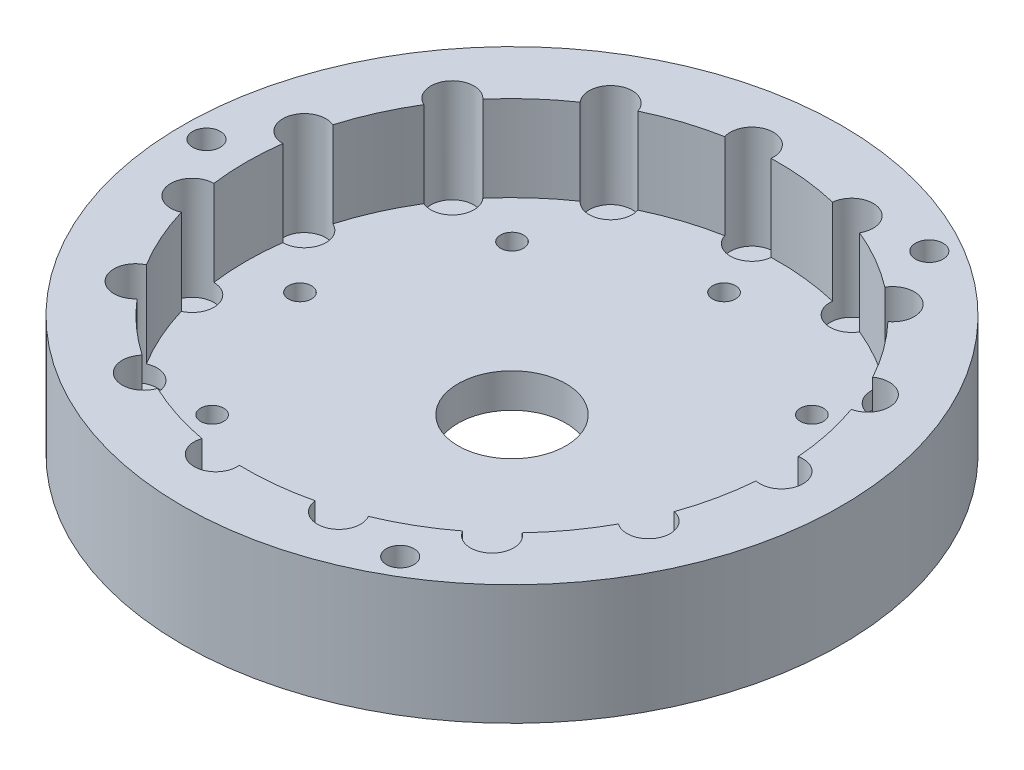
SolidWorks part; units mm, degrees
ref_plane "Front Plane" through (0, 0, 0) normal (0, 0, 1) x (1, 0, 0)
ref_plane "Top Plane" through (0, 0, 0) normal (0, 1, 0) x (1, 0, 0)
ref_plane "Right Plane" through (0, 0, 0) normal (1, 0, 0) x (0, 0, -1)
sketch "Sketch1" plane through (0, 0, 0) normal (0, 1, 0) x (1, 0, 0)
  line L0 (0, 0) -> (-42.5, 0) construction
  circle A0 centre (0, 0) radius 7.5
  circle A1 centre (0, 0) radius 45.85
  circle A2 centre (0, 0) radius 37.5 construction
  circle A3 centre (37.5, 0) radius 3
  circle A4 centre (34.258, 15.2526) radius 3
  circle A5 centre (25.0924, 27.8679) radius 3
  circle A6 centre (11.5881, 35.6646) radius 3
  circle A7 centre (-3.9198, 37.2946) radius 3
  circle A8 centre (-18.75, 32.476) radius 3
  circle A9 centre (-30.3381, 22.0419) radius 3
  circle A10 centre (-36.6805, 7.7967) radius 3
  circle A11 centre (-36.6805, -7.7967) radius 3
  circle A12 centre (-30.3381, -22.0419) radius 3
  circle A13 centre (-18.75, -32.476) radius 3
  circle A14 centre (-3.9198, -37.2946) radius 3
  circle A15 centre (11.5881, -35.6646) radius 3
  circle A16 centre (25.0924, -27.8679) radius 3
  circle A17 centre (34.258, -15.2526) radius 3
  circle A19 centre (0, 0) radius 29.5 construction
  circle A20 centre (29.5, 0) radius 1.607
  circle A21 centre (20.8597, -20.8597) radius 1.607
  circle A22 centre (0, -29.5) radius 1.607
  circle A23 centre (-20.8597, -20.8597) radius 1.607
  circle A24 centre (-29.5, 0) radius 1.607
  circle A25 centre (-20.8597, 20.8597) radius 1.607
  circle A26 centre (0, 29.5) radius 1.607
  circle A27 centre (20.8597, 20.8597) radius 1.607
  arc A28 (36.8833, 2.9359) -> (34.8888, 12.3197) centre (0, 0) ccw
  arc A29 (34.8888, -12.3197) -> (36.8833, -2.9359) centre (0, 0) ccw
  arc A30 (26.8616, -25.4451) -> (32.5004, -17.6839) centre (0, 0) ccw
  arc A31 (14.1898, -34.1709) -> (22.4979, -29.3742) centre (0, 0) ccw
  arc A32 (-0.9355, -36.9882) -> (8.6053, -35.9854) centre (0, 0) ccw
  arc A33 (-15.8991, -33.4099) -> (-6.7752, -36.3744) centre (0, 0) ccw
  arc A34 (-28.1135, -24.0547) -> (-20.9843, -30.4739) centre (0, 0) ccw
  arc A35 (-35.4669, -10.5403) -> (-31.5649, -19.3043) centre (0, 0) ccw
  arc A36 (-36.6878, 4.7967) -> (-36.6878, -4.7967) centre (0, 0) ccw
  arc A37 (-31.5649, 19.3043) -> (-35.4669, 10.5403) centre (0, 0) ccw
  arc A38 (-20.9843, 30.4739) -> (-28.1135, 24.0547) centre (0, 0) ccw
  arc A39 (-6.7752, 36.3744) -> (-15.8991, 33.4099) centre (0, 0) ccw
  arc A40 (8.6053, 35.9854) -> (-0.9355, 36.9882) centre (0, 0) ccw
  arc A41 (22.4979, 29.3742) -> (14.1898, 34.1709) centre (0, 0) ccw
  arc A42 (32.5004, 17.6839) -> (26.8616, 25.4451) centre (0, 0) ccw
  circle A43 centre (-42.5, 0) radius 1.5635
  circle A44 centre (21.25, 36.8061) radius 1.5635
  circle A45 centre (21.25, -36.8061) radius 1.5635
  point P38 (0, 0)
  point P57 (0, 0)
  point P87 (0, 0)
  point P92 (0, 0)
  dimension "D2" = 15
  dimension "D3" = 75
  dimension "D4" = 91.7
  dimension "D5" = 6
  dimension "D8" = 3.214
  dimension "D9" = 59
  dimension "D6" = 37
  dimension "D12" = 3.127
  dimension "D11" = 42.5
  dimension "D1" = 15
  dimension "D7" = 8
  dimension "D10" = 15
  dimension "D13" = 3
extrude "Boss-Extrude1" add sketch "Sketch1" against normal blind 4.7625 contours A4 A42 A5 A41 A6 A40 A7 A39 A8 A38 A9 A37 A10 A36 A11 A35 A12 A34 A13 A33 A14 A32 A15 A31 A16 A30 A17 A29 A3 A28 A0 A20 A21 A22 A23 A24 A25 A26 A27 | A3 | A17 | A4 | A5 | A6 | A7 | A8 | A9 | A10 | A11 | A12 | A13 | A14 | A15 | A16 | A1 A42 A4 A28 A3 A29 A17 A30 A16 A31 A15 A32 A14 A33 A13 A34 A12 A35 A11 A36 A10 A37 A9 A38 A8 A39 A7 A40 A6 A41 A5 | A22 | A23 | A24 | A25 | A26 | A27 | A20 | A21 region at (-44.5532, 0, 0) region at (37.5, 0, 0) region at (33.4543, 0, 0) region at (34.258, 0, -15.2526) region at (34.258, 0, 15.2526) region at (25.0924, 0, -27.8679) region at (25.0924, 0, 27.8679) region at (11.5881, 0, -35.6646) region at (11.5881, 0, 35.6646) region at (-3.9198, 0, -37.2946) region at (-3.9198, 0, 37.2946) region at (-18.75, 0, -32.476) region at (-18.75, 0, 32.476) region at (-30.3381, 0, -22.0419) region at (-30.3381, 0, 22.0419) region at (-36.6805, 0, -7.7967) region at (-36.6805, 0, 7.7967) region at (29.5, 0, 0) region at (20.8597, 0, 20.8597) region at (0, 0, 29.5) region at (-20.8597, 0, 20.8597) region at (-29.5, 0, 0) region at (-20.8597, 0, -20.8597) region at (0, 0, -29.5) region at (20.8597, 0, -20.8597)
extrude "Cut-Extrude1" cut sketch "Sketch1<6>" against normal blind 2.4105 contours A24 | A25 | A26 | A27 | A20 | A21 | A22 | A23 | A10 | A11 | A9 | A12 | A13 | A14 | A15 | A16 | A17 | A3 | A4 | A5 | A6 | A7 | A8 region at (37.5, 0, 0) region at (34.258, 0, -15.2526) region at (34.258, 0, 15.2526) region at (25.0924, 0, -27.8679) region at (25.0924, 0, 27.8679) region at (11.5881, 0, -35.6646) region at (11.5881, 0, 35.6646) region at (-3.9198, 0, -37.2946) region at (-3.9198, 0, 37.2946) region at (-18.75, 0, -32.476) region at (-18.75, 0, 32.476) region at (-30.3381, 0, -22.0419) region at (-30.3381, 0, 22.0419) region at (-36.6805, 0, -7.7967) region at (-36.6805, 0, 7.7967) region at (29.5, 0, 0) region at (20.8597, 0, 20.8597) region at (0, 0, 29.5) region at (-20.8597, 0, 20.8597) region at (-29.5, 0, 0) region at (-20.8597, 0, -20.8597) region at (0, 0, -29.5) region at (20.8597, 0, -20.8597)
sketch "Sketch1<6>" plane through (0, 0, 0) normal (0, 1, 0) x (1, 0, 0) same geometry as "Sketch1"
extrude "Boss-Extrude2" add sketch "Sketch1<7>" along normal blind 11.9355 contours A1 A42 A4 A28 A3 A29 A17 A30 A16 A31 A15 A32 A14 A33 A13 A34 A12 A35 A11 A36 A10 A37 A9 A38 A8 A39 A7 A40 A6 A41 A5 region at (-44.5532, 0, 0)
sketch "Sketch1<7>" plane through (0, 0, 0) normal (0, 1, 0) x (1, 0, 0) same geometry as "Sketch1"
sketch "Sketch2" plane through (0, 11.9355, 0) normal (0, 1, 0) x (1, 0, 0)
  circle A0 centre (-42.5, 0) radius 1.925
  circle A1 centre (21.25, 36.8061) radius 1.925
  circle A2 centre (21.25, -36.8061) radius 1.925
  point P10 (0, 0)
  dimension "D2" = 3.85
  dimension "D1" = 3
extrude "Cut-Extrude2" cut sketch "Sketch2" against normal blind 4
equation "\"D2@Sketch1\"=\"smallBearOD\"+\"smallBearOTight\""
equation "\"D3@Sketch1\"=\"pinCircleDiam\""
equation "\"D5@Sketch1\"=\"pinDiam\""
equation "\"D8@Sketch1\"=\"ballBearDiam\""
equation "\"D1@Cut-Extrude1\"=\"ballBearDiam\"*0.75"
equation "\"D1@Boss-Extrude2\"=\"ballBearDiam\"*0.75mm+2*\"sheetThickness\""
equation "\"largeBearOD\"= 21mm"
equation "\"largeBearID\" = 15mm"
equation "\"largeBearOTight\"= 0.127mm'calibrate - hold onto gears"
equation "\"largeBearITight\"= 0mm'calibrate - hold onto eccentric nut"
equation "\"largeBearFlangeDiam\" = 22.5mm"
equation "\"largeBearFlangeWidth\" = 0.8mm"
equation "\"smallBearOD\"= 15mm"
equation "\"smallBearOTight\"= 0mm'calibrate - hold onto bottom of gearbox"
equation "\"smallBearOLoose\"= 0mm'calibrate - able to take off topHat"
equation "\"smallBearID\" = 10mm"
equation "\"smallBearITight\" = 0mm'hold onto "
equation "\"pinCircleDiam\"= 75mm"
equation "\"pinDiam\"= 6mm"
equation "\"sheetThickness\"= 0.1875in"
equation "\"ballBearDiam\"= 3.214mm"
equation "\"thrustBearingThickness\"= 5mm'measure this irl and change"
equation "\"thrustBearingID\"= 0mm'measure this irl and change"
equation "\"thrustBearingOD\"= 0mm'measure this irl and change"
equation "\"eccentricity\" = 1mm"
equation "\"D6@Sketch1\"=(\"pinCircleDiam\"-1)/2"
equation "\"D1@Boss-Extrude1\"=\"sheetThickness\""
